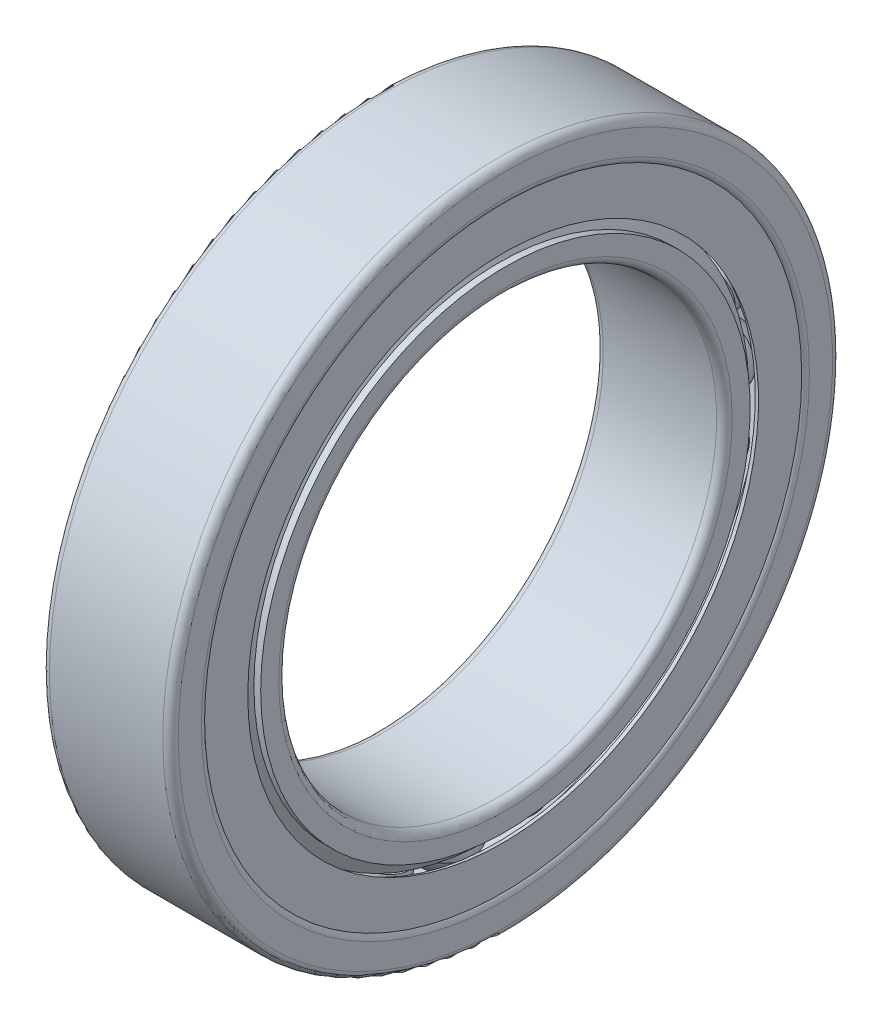
SolidWorks part; units mm, degrees
ref_plane "前视基准面" through (0, 0, 0) normal (0, 0, 1) x (1, 0, 0)
ref_plane "上视基准面" through (0, 0, 0) normal (0, 1, 0) x (1, 0, 0)
ref_plane "右视基准面" through (0, 0, 0) normal (1, 0, 0) x (0, 0, -1)
sketch "尺寸草图" plane through (0, 0, 0) normal (0, 0, 1) x (1, 0, 0)
  line L0 (-19.9271, 0) -> (19.9271, 0) construction
  line L1 (0, 21.603) -> (0, -21.603) construction
  line L2 (-2.2, 13) -> (2.2, 13)
  line L3 (2.5, 12.7) -> (2.5, 11.8)
  line L4 (-2.5, 12.7) -> (-2.5, 11.8)
  line L5 (-2.2, 11.5) -> (2.2, 11.5)
  line L6 (-3.5, 10.75) -> (3.3577, 10.75) construction
  line L7 (-2.2, 10) -> (2.2, 10)
  line L8 (2.5, 9.7) -> (2.5, 8.8)
  line L9 (2.2, 8.5) -> (-2.2, 8.5)
  line L10 (-2.5, 8.8) -> (-2.5, 9.7)
  line L11 (0, 10.75) -> (0, 11.875) construction
  line L13 (2.2, 11.5) -> (2.2, 10)
  line L14 (1.95, 10) -> (2.2387, 9.5)
  line L15 (2.2387, 9.5) -> (2.5, 9.5)
  line L16 (2.4121, 11.5879) -> (2.4121, 9.9121)
  circle A0 centre (0, 10.75) radius 1.125
  arc A1 (2.5, 11.8) -> (2.2, 11.5) centre (2.2, 11.8) cw
  arc A2 (2.5, 9.7) -> (2.2, 10) centre (2.2, 9.7) ccw
  arc A3 (-2.2, 10) -> (-2.5, 9.7) centre (-2.2, 9.7) ccw
  arc A4 (-2.2, 11.5) -> (-2.5, 11.8) centre (-2.2, 11.8) cw
  arc A5 (-2.2, 8.5) -> (-2.5, 8.8) centre (-2.2, 8.8) cw
  arc A6 (2.2, 8.5) -> (2.5, 8.8) centre (2.2, 8.8) ccw
  arc A7 (2.5, 12.7) -> (2.2, 13) centre (2.2, 12.7) ccw
  arc A8 (-2.2, 13) -> (-2.5, 12.7) centre (-2.2, 12.7) ccw
  point P7 (0, 0)
  point P25 (-2.5, 10)
  point P28 (-2.5, 11.5)
  point P31 (-2.5, 8.5)
  point P36 (2.5, 13)
  point P39 (-2.5, 13)
  dimension "D1" = 0.375
  dimension "D3" = 0.3
  dimension "B" = 5
  dimension "D2" = 2.5
  dimension "D" = 26
  dimension "(d)" = 17
  dimension "D5" = 10.75
  dimension "D6" = 1.5
  dimension "D7" = 1.5
  dimension "D8" = 0.5
  dimension "D9" = 60
  dimension "D10" = 0.55
sketch "草图2" plane through (0, 0, 0) normal (0, 0, 1) x (1, 0, 0)
  line L0 (1.95, 10) -> (2.2387, 9.5) construction
  line L1 (2.2387, 9.5) -> (2.5, 9.5) construction
  line L2 (1.95, 10) -> (2.2387, 9.5)
  line L3 (2.2387, 9.5) -> (2.5, 9.5)
  line L4 (0, 11.875) -> (0, 9.625) construction
  line L5 (-2.2387, 9.5) -> (-2.5, 9.5)
  line L6 (2.2, 8.5) -> (-2.2, 8.5) construction
  line L7 (-1.95, 10) -> (-2.2387, 9.5)
  line L8 (-2.5, 12.7) -> (-2.5, 11.8) construction
  line L9 (-2.2, 11.5) -> (2.2, 11.5) construction
  line L10 (-2.2, 13) -> (2.2, 13) construction
  line L11 (2.5, 12.7) -> (2.5, 11.8) construction
  line L12 (2.5, 9.7) -> (2.5, 8.8) construction
  line L13 (-2.2, 10) -> (2.2, 10) construction
  line L14 (2.2, 8.5) -> (-2.2, 8.5)
  line L15 (-2.5, 8.8) -> (-2.5, 9.7) construction
  line L18 (-3.5, 0) -> (3.5, 0) construction
  line L19 (-19.9271, 0) -> (19.9271, 0) construction
  line L20 (-2.5, 12.7) -> (-2.5, 11.8)
  line L21 (-2.2, 11.5) -> (-0.8385, 11.5)
  line L22 (-2.2, 13) -> (2.2, 13)
  line L23 (2.5, 12.7) -> (2.5, 11.8)
  line L24 (2.5, 9.5) -> (2.5, 8.8)
  line L25 (-1.95, 10) -> (-0.8385, 10)
  line L26 (-2.5, 8.8) -> (-2.5, 9.5)
  line L27 (0.8385, 11.5) -> (2.2, 11.5)
  line L28 (0.8385, 10) -> (1.95, 10)
  circle A0 centre (0, 10.75) radius 1.125 construction
  arc A1 (0.8385, 11.5) -> (-0.8385, 11.5) centre (0, 10.75) ccw
  arc A2 (-0.8385, 10) -> (0.8385, 10) centre (0, 10.75) ccw
  arc A3 (-2.2, 13) -> (-2.5, 12.7) centre (-2.2, 12.7) ccw construction
  arc A4 (-2.5, 11.8) -> (-2.2, 11.5) centre (-2.2, 11.8) ccw construction
  arc A5 (2.5, 12.7) -> (2.2, 13) centre (2.2, 12.7) ccw construction
  arc A6 (2.2, 11.5) -> (2.5, 11.8) centre (2.2, 11.8) ccw construction
  arc A8 (2.2, 8.5) -> (2.5, 8.8) centre (2.2, 8.8) ccw construction
  arc A10 (-2.5, 8.8) -> (-2.2, 8.5) centre (-2.2, 8.8) ccw construction
  arc A11 (-2.2, 13) -> (-2.5, 12.7) centre (-2.2, 12.7) ccw
  arc A12 (-2.5, 11.8) -> (-2.2, 11.5) centre (-2.2, 11.8) ccw
  arc A13 (2.5, 12.7) -> (2.2, 13) centre (2.2, 12.7) ccw
  arc A14 (2.2, 11.5) -> (2.5, 11.8) centre (2.2, 11.8) ccw
  arc A16 (2.2, 8.5) -> (2.5, 8.8) centre (2.2, 8.8) ccw
  arc A18 (-2.5, 8.8) -> (-2.2, 8.5) centre (-2.2, 8.8) ccw
revolve "旋转1" add sketch "草图2" angle 360 about L18
sketch "草图5" plane through (0, 0, 0) normal (0, 0, 1) x (1, 0, 0)
  line L1 (-0.3375, 10.525) -> (0.3375, 10.525)
  line L2 (-0.3375, 10.525) -> (-0.3375, 10.975)
  line L3 (-0.3375, 10.975) -> (0.3375, 10.975)
  line L4 (0.3375, 10.525) -> (0.3375, 10.975)
  line L5 (-0.3375, 10.525) -> (0.3375, 10.975) construction
  line L6 (-0.3375, 10.975) -> (0.3375, 10.525) construction
  circle A0 centre (0, 10.75) radius 1.125 construction
  circle A1 centre (0, 10.75) radius 1.125 construction
  point P0 (0, 10.75)
  dimension "D3" = 2.25
  dimension "D1" = 0.675
  dimension "D2" = 0.45
revolve "旋转3" add sketch "草图5" angle 360 about L0
sketch "草图3" plane through (0, 0, 0) normal (0, 0, 1) x (1, 0, 0)
  line L1 (-1.2375, 10.75) -> (1.2375, 10.75)
  circle A0 centre (0, 10.75) radius 1.125 construction
  circle A1 centre (0, 10.75) radius 1.125 construction
  arc A2 (1.2375, 10.75) -> (-1.2375, 10.75) centre (0, 10.75) ccw
  dimension "D2" = 2.475
revolve "旋转2" add sketch "草图3" angle 360 about L1 region at (0, 11.2752, 0)
ref_axis "基准轴1" through (-3.85, 0, 0) along (1, 0, 0)
pattern_circular "阵列(圆周)5" count 24 over 360 about axis through (-3.85, 0, 0) along (1, 0, 0) of bodies 103
sketch "草图6" plane through (0, 0, 0) normal (0, 0, 1) x (1, 0, 0)
  line L0 (-1.2169, 10.975) -> (1.2169, 10.975)
  line L1 (-3.5, 10.75) -> (2.5, 10.75) construction
  line L3 (-1.2169, 10.525) -> (1.2169, 10.525)
  line L4 (2.5, -12.7) -> (2.5, 12.7) construction
  arc A0 (-1.2169, 10.525) -> (1.2169, 10.525) centre (0, 10.75) ccw
  circle A1 centre (0, 10.75) radius 1.125 construction
  circle A2 centre (0, 10.75) radius 1.125 construction
  arc A3 (1.2169, 10.975) -> (-1.2169, 10.975) centre (0, 10.75) ccw
  dimension "D1" = 2.475
  dimension "D2" = 2.25
  dimension "D3" = 0.225
  dimension "D4" = 0.225
revolve "切除-旋转1" cut sketch "草图6" angle 360 about L0
sketch "草图7" plane through (0, 0, 0) normal (0, 0, 1) x (1, 0, 0)
  line L0 (-1.125, 10.75) -> (1.125, 10.75)
  line L1 (-2.5, 0) -> (2.4587, 0) construction
  line L2 (-2.5, 12.7) -> (-2.5, -12.7) construction
  line L3 (-19.9271, 0) -> (19.9271, 0) construction
  circle A0 centre (0, 10.75) radius 1.125 construction
  arc A1 (1.125, 10.75) -> (-1.125, 10.75) centre (0, 10.75) ccw
revolve "旋转4" add sketch "草图7" angle 360 about L0
pattern_circular "阵列(圆周)2" count 24 over 360 about axis through (-3.85, 0, 0) along (1, 0, 0) of "旋转4" reverse direction yes
sketch "草图9" plane through (0, 0, 0) normal (0, 0, 1) x (1, 0, 0)
  line L1 (2.2, 11.5) -> (2.2, 10) construction
  line L4 (2.4121, 11.5879) -> (2.4121, 9.9121) construction
  line L5 (2.2, 11.5) -> (2.2, 10)
  line L6 (2.4121, 11.5879) -> (2.4121, 9.9121)
  line L7 (-2.4121, 11.5879) -> (-2.4121, 9.9121)
  line L8 (0, 13) -> (0, 0) construction
  line L9 (-2.2, 13) -> (2.2, 13) construction
  line L10 (-2.2, 11.5) -> (-2.2, 10)
  arc A0 (2.2, 11.5) -> (2.5, 11.8) centre (2.2, 11.8) ccw construction
  arc A1 (2.2, 11.5) -> (2.4121, 11.5879) centre (2.2, 11.8) ccw
  arc A2 (2.5, 9.7) -> (2.2, 10) centre (2.2, 9.7) ccw construction
  arc A3 (2.4121, 9.9121) -> (2.2, 10) centre (2.2, 9.7) ccw
  arc A4 (-2.4121, 9.9121) -> (-2.2, 10) centre (-2.2, 9.7) cw
  arc A5 (-2.2, 11.5) -> (-2.4121, 11.5879) centre (-2.2, 11.8) cw
revolve "旋转5" add sketch "草图9" angle 360 about L0
